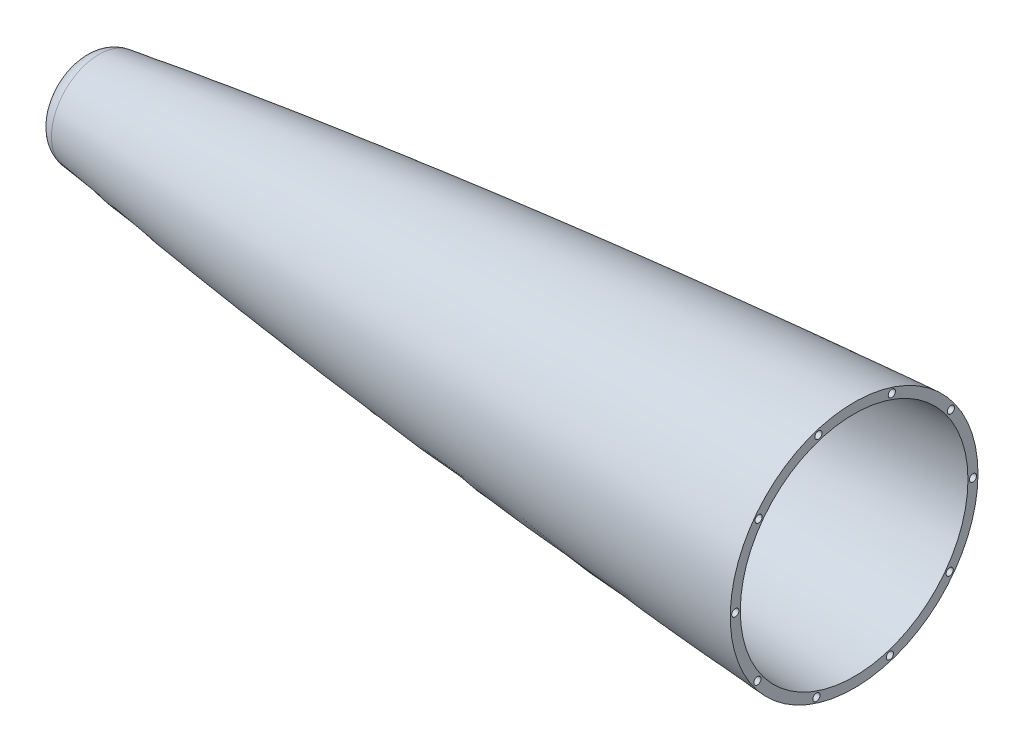
SolidWorks part; units mm, degrees
ref_plane "Front Plane" through (0, 0, 0) normal (0, 0, 1) x (1, 0, 0)
ref_plane "Top Plane" through (0, 0, 0) normal (0, 1, 0) x (1, 0, 0)
ref_plane "Right Plane" through (0, 0, 0) normal (1, 0, 0) x (0, 0, -1)
sketch "Sketch1" plane through (0, 0, 0) normal (0, 0, 1) x (1, 0, 0)
  line L2 (0, -76.2) -> (-921.7152, -76.2) construction
  line L3 (6.35, 6.35) -> (6.35, 0)
  line L4 (-259.8125, 11.4606) -> (6.35, 11.4606)
  line L5 (0, 0) -> (6.35, 0)
  line L6 (6.35, 6.35) -> (6.35, -76.2) construction
  line L7 (0, 0) -> (0, -76.2) construction
  line L8 (-921.7152, -58.5997) -> (-928.0652, -58.5997)
  line L9 (-928.0652, -58.5997) -> (-928.0652, -76.2) construction
  line L10 (-921.7152, -58.5997) -> (-921.7152, -76.2) construction
  line L11 (6.35, 11.4606) -> (6.35, 6.35)
  arc A0 (-254, 2.1118) -> (-248.4137, -0.891) centre (-248.6021, 5.4563) ccw
  arc A2 (-916.3053, -52.3197) -> (-921.7152, -58.5997) centre (-915.3652, -58.5997) ccw
  arc A4 (-254, 2.1118) -> (-259.6052, 5.114) centre (-259.3979, -1.2327) ccw
  arc A6 (-248.6021, 5.4563) -> (-248.6021, 5.4563) centre (-248.6021, 5.4563) ccw
  arc A7 (-248.6021, 5.4563) -> (-259.8125, 11.4606) centre (-259.3979, -1.2327) ccw
  arc A8 (-917.2454, -46.0396) -> (-928.0652, -58.5997) centre (-915.3652, -58.5997) ccw
  spline S0 degree 3 poles (0, 0) (-50.8, 0) (-101.6, 0) (-157.1824, 0) (-166.7471, 0) (-181.0943, 0) (-190.659, 0) (-199.5851, 0) (-207.8726, 0) (-220.3048, -0.155) (-228.5897, -0.3615) (-235.0947, -0.5237) (-239.8196, -0.6415) (-245.0466, -0.7915) (-247.9113, -0.876) (-248.4137, -0.891) knots 0.761574 0.761574 0.761574 0.761574 0.907842 0.907842 0.921611 0.935381 0.949151 0.949151 0.961082 0.973013 0.984944 0.984944 0.991748 0.998553 1 1 1 1
  spline S1 degree 1 poles (6.35, 6.35) (-248.6021, 5.4563) knots 0 0 1 1 construction
  spline S2 degree 3 poles (-259.6052, 5.114) (-267.1277, 4.8682) (-283.426, 4.2857) (-317.2703, 2.8805) (-361.13, 0.7112) (-431.2755, -3.372) (-501.3729, -8.2669) (-571.4145, -13.8917) (-623.9147, -18.4777) (-676.3803, -23.4393) (-728.8057, -28.7991) (-772.4536, -33.6275) (-807.3418, -37.7392) (-833.4907, -40.9589) (-859.6194, -44.3289) (-885.7239, -47.8693) (-904.6125, -50.5779) (-914.801, -52.0945) (-916.3053, -52.3197) knots 0.121539 0.121539 0.121539 0.121539 0.143123 0.168303 0.218664 0.269025 0.369746 0.420107 0.470467 0.520828 0.571189 0.62155 0.64673 0.67191 0.697091 0.722271 0.747451 0.751814 0.751814 0.751814 0.751814
  spline S3 degree 1 poles (-259.8125, 11.4606) (-917.2454, -46.0396) knots 0 0 1 1 construction
  spline S4 degree 3 poles (6.35, 6.35) (-14.881, 6.35) (-57.3424, 6.3506) (-110.4226, 6.3484) (-152.8795, 6.3528) (-179.4314, 6.3414) (-200.6356, 6.3648) (-216.6826, 6.282) (-232.6614, 5.8947) (-243.2867, 5.614) (-248.6021, 5.4563) knots 0.75548 0.75548 0.75548 0.75548 0.81661 0.87774 0.908305 0.93887 0.954152 0.969435 0.984717 1 1 1 1
  spline S5 degree 3 poles (-259.8125, 11.4606) (-287.3121, 10.5623) (-342.298, 8.1716) (-452.1401, 1.8335) (-589.2803, -8.5121) (-726.1766, -21.7709) (-835.4658, -34.5887) (-890.027, -41.9652) (-917.2454, -46.0396) knots 0.121539 0.121539 0.121539 0.121539 0.200324 0.279108 0.436676 0.594245 0.673029 0.751814 0.751814 0.751814 0.751814
revolve "Revolve1" add sketch "Sketch1" angle 360 about L2 region at (-124.3289, 8.8839, 0) region at (-3.0204, 3.175, 0)
ref_plane "Plane1" through (-438.15, 0, 0) normal (1, 0, 0) x (0, 0, -1)
sketch "Sketch8" plane through (-438.15, 0, 0) normal (1, 0, 0) x (0, 0, -1)
  circle A0 centre (0, -76.2) radius 87.6606 construction
  circle A1 centre (0, -76.2) radius 87.6606 construction
  circle A2 centre (0, -76.2) radius 142.3459
extrude "Cut-Extrude4" cut sketch "Sketch8" along normal through all
sketch "Sketch9" plane through (-438.15, 0, 0) normal (1, 0, 0) x (0, 0, -1)
  line L0 (0, 0) -> (0, -76.2) construction
  line L1 (0, -76.2) -> (23.926, -4.6927) construction
  circle A0 centre (0, -76.2) radius 72.2219 construction
  circle A1 centre (0, -76.2) radius 78.586 construction
  circle A2 centre (0, -76.2) radius 72.2219 construction
  circle A3 centre (0, -76.2) radius 78.586 construction
  circle A4 centre (0, -76.2) radius 75.4039 construction
  circle A5 centre (23.926, -4.6927) radius 2.286
  circle A6 centre (61.3875, -32.4127) radius 2.286
  circle A7 centre (75.4011, -76.858) radius 2.286
  circle A8 centre (60.614, -121.052) radius 2.286
  circle A9 centre (22.6744, -148.114) radius 2.286
  circle A10 centre (-23.926, -147.7073) radius 2.286
  circle A11 centre (-61.3875, -119.9873) radius 2.286
  circle A12 centre (-75.4011, -75.542) radius 2.286
  circle A13 centre (-60.614, -31.348) radius 2.286
  circle A14 centre (-22.6744, -4.286) radius 2.286
  point P31 (0, -76.2)
  dimension "D1" = 6.364
  dimension "D2" = 3.182
  dimension "D3" = 4.572
  dimension "D4" = 18.5
  dimension "D5" = 10
extrude "Cut-Extrude5" cut sketch "Sketch9" against normal blind 10.16
